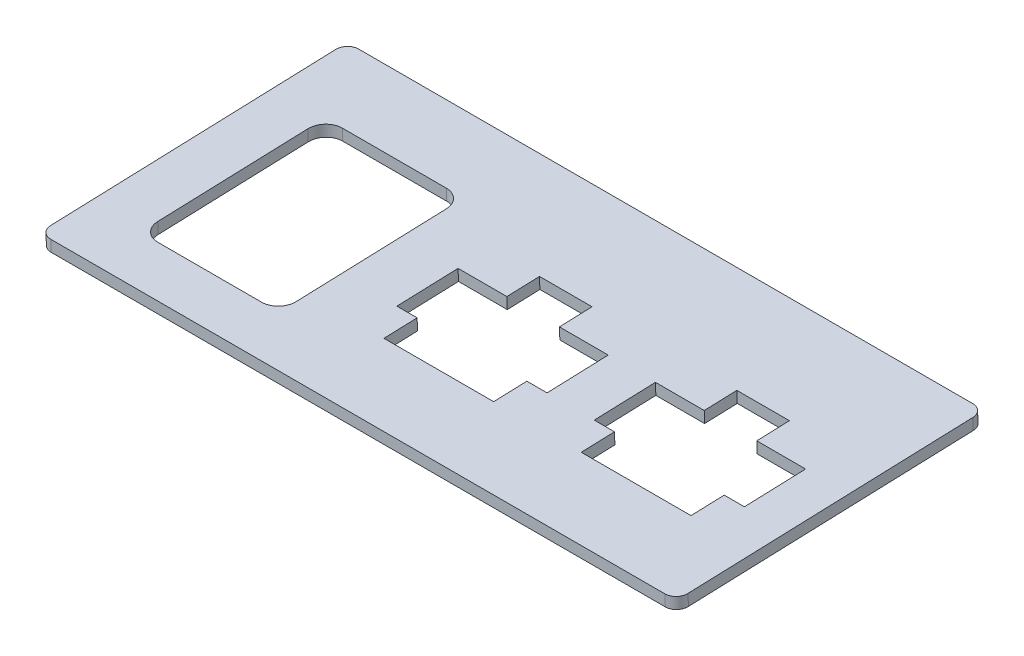
SolidWorks part; units mm, degrees
ref_plane "Front Plane" through (0, 0, 0) normal (0, 0, 1) x (1, 0, 0)
ref_plane "Top Plane" through (0, 0, 0) normal (0, 1, 0) x (1, 0, 0)
ref_plane "Right Plane" through (0, 0, 0) normal (1, 0, 0) x (0, 0, -1)
sketch "Sketch1" plane through (0, -69.2407, -2.4179) normal (0, 0.9994, 0.0349) x (1, 0, 0)
  line L1 (-52.175, -2.8069) -> (-56.175, -2.8069) construction
  line L2 (55.275, 49.0443) -> (-55.275, 49.0443) construction
  line L8 (-55.175, -4.3069) -> (55.175, -4.3069)
  line L9 (55.175, -4.3069) -> (55.175, 49.0443)
  line L10 (55.175, 49.0443) -> (-55.175, 49.0443)
  line L11 (-55.175, 49.0443) -> (-55.175, -4.3069)
  dimension "D1" = 1.5
  dimension "D2" = 3
  dimension "D5" = 3
extrude "Boss-Extrude1" add sketch "Sketch1" along normal blind 2
sketch "Sketch2" plane through (0, -69.2407, -2.4179) normal (0, -0.9994, -0.0349) x (1, 0, 0)
  line L0 (-4.05, -25.5688) -> (-4.05, -31.2188)
  line L1 (-43.175, -4.2188) -> (-25.175, -4.2188)
  line L2 (-46.175, -7.2188) -> (-46.175, -33.2188)
  line L3 (-43.175, -36.2188) -> (-25.175, -36.2188)
  line L4 (-22.175, -7.2188) -> (-22.175, -33.2188)
  line L5 (-12.5, -14.9688) -> (-9, -14.9688)
  line L6 (-12.5, -14.9688) -> (-12.5, -25.5688)
  line L7 (-12.5, -25.5688) -> (-4.05, -25.5688)
  line L8 (13.5, -14.9688) -> (13.5, -25.5688)
  line L9 (-9, -9.2188) -> (10, -9.2188)
  line L10 (-9, -9.2188) -> (-9, -14.9688)
  line L11 (-4.05, -31.2188) -> (5.05, -31.2188)
  line L12 (10, -9.2188) -> (10, -14.9688)
  line L13 (10, -14.9688) -> (13.5, -14.9688)
  line L14 (5.05, -25.5688) -> (5.05, -31.2188)
  line L15 (5.05, -25.5688) -> (13.5, -25.5688)
  line L16 (-13, -6.7188) -> (14, -33.7188) construction
  line L17 (-13, -6.7188) -> (14, -6.7188) construction
  line L18 (-13, -6.7188) -> (-13, -33.7188) construction
  line L19 (-13, -33.7188) -> (14, -33.7188) construction
  line L20 (14, -6.7188) -> (14, -33.7188) construction
  line L21 (17.5875, 3.7502) -> (17.5875, -36.664) construction
  line L22 (47.675, -20.2688) -> (21.675, -20.2688) construction
  line L23 (34.675, -9.2188) -> (34.675, -31.2188) construction
  line L24 (21.175, -6.7188) -> (21.175, -33.7188) construction
  line L25 (48.175, -33.7188) -> (21.175, -33.7188) construction
  line L26 (48.175, -6.7188) -> (48.175, -33.7188) construction
  line L27 (48.175, -6.7188) -> (21.175, -6.7188) construction
  line L28 (-48.175, -20.2188) -> (-46.175, -20.2188) construction
  line L29 (-48.175, -2.2188) -> (-20.175, -2.2188) construction
  line L30 (-48.175, -2.2188) -> (-48.175, -38.2188) construction
  line L31 (-48.175, -38.2188) -> (-20.175, -38.2188) construction
  line L32 (-20.175, -2.2188) -> (-20.175, -38.2188) construction
  line L33 (-34.175, -4.2188) -> (-34.175, -2.2188) construction
  line L34 (0.5, -9.2188) -> (0.5, -31.2188) construction
  line L35 (-12.5, -20.2688) -> (13.5, -20.2688) construction
  line L36 (48.175, -6.7188) -> (21.175, -33.7188) construction
  line L37 (30.125, -25.5688) -> (21.675, -25.5688)
  line L38 (30.125, -25.5688) -> (30.125, -31.2188)
  line L39 (25.175, -14.9688) -> (21.675, -14.9688)
  line L40 (25.175, -9.2188) -> (25.175, -14.9688)
  line L41 (39.225, -31.2188) -> (30.125, -31.2188)
  line L42 (44.175, -9.2188) -> (44.175, -14.9688)
  line L43 (44.175, -9.2188) -> (25.175, -9.2188)
  line L44 (21.675, -14.9688) -> (21.675, -25.5688)
  line L45 (47.675, -25.5688) -> (39.225, -25.5688)
  line L46 (47.675, -14.9688) -> (47.675, -25.5688)
  line L47 (47.675, -14.9688) -> (44.175, -14.9688)
  line L48 (39.225, -25.5688) -> (39.225, -31.2188)
  line L49 (21.175, -20.2188) -> (14, -20.2188) construction
  line L50 (-55.175, 4.3069) -> (55.175, 4.3069) construction
  line L51 (48.175, -20.2188) -> (52.175, -20.2188) construction
  line L52 (55.175, 4.3069) -> (55.175, -49.0443) construction
  line L53 (-46.6517, -44.7445) -> (46.6517, -44.7445) construction
  line L54 (-13, -20.2188) -> (-20.175, -20.2188) construction
  line L55 (-34.175, -2.2188) -> (-34.175, 4.3069) construction
  line L56 (-34.175, -38.2188) -> (-34.175, -44.7445) construction
  line L57 (-55.175, -49.0443) -> (-55.175, 4.3069) construction
  line L58 (-48.175, -20.2188) -> (-52.175, -20.2188) construction
  arc A0 (-46.175, -33.2188) -> (-43.175, -36.2188) centre (-43.175, -33.2188) ccw
  arc A1 (-25.175, -36.2188) -> (-22.175, -33.2188) centre (-25.175, -33.2188) ccw
  arc A2 (-25.175, -4.2188) -> (-22.175, -7.2188) centre (-25.175, -7.2188) cw
  arc A3 (-43.175, -4.2188) -> (-46.175, -7.2188) centre (-43.175, -7.2188) ccw
  point P28 (0.5, -20.2188)
  point P63 (34.675, -20.2188)
  dimension "D1" = 3
  dimension "D2" = 32
  dimension "D3" = 24
  dimension "D4" = 28
  dimension "D5" = 36
  dimension "D6" = 26
  dimension "D7" = 22
  dimension "D8" = 10.6
  dimension "D9" = 19
  dimension "D10" = 9.1
  dimension "D11" = 5.75
  dimension "D12" = 27
  dimension "D13" = 27
  dimension "D14" = 4
  dimension "D15" = 3
  dimension "D16" = 3
extrude "Cut-Extrude1" cut sketch "Sketch2" against normal up to next
fillet "Fillet1" radius 2 4 edges at (-55.175, -68.3916, 1.9212) (55.175, -68.3916, 1.9212) (55.175, -66.5297, -51.3974) (-55.175, -66.5297, -51.3974)
